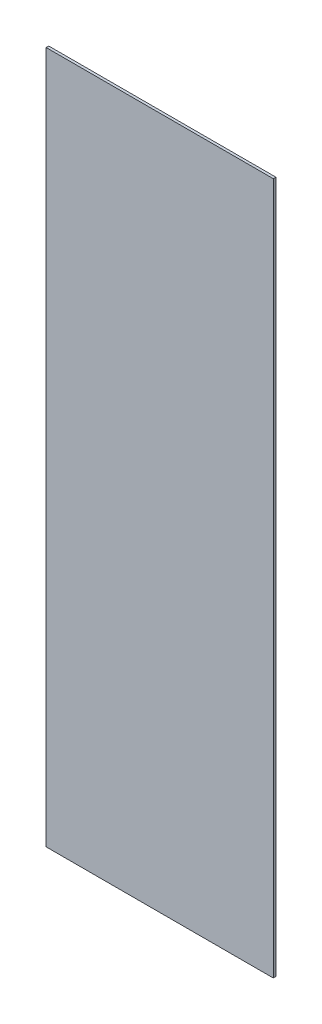
SolidWorks part; units mm, degrees
material "1060 Alloy"
ref_plane "Front Plane" through (0, 0, 0) normal (0, 0, 1) x (1, 0, 0)
ref_plane "Top Plane" through (0, 0, 0) normal (0, 1, 0) x (1, 0, 0)
ref_plane "Right Plane" through (0, 0, 0) normal (1, 0, 0) x (0, 0, -1)
sketch "Sketch1" plane through (0, 0, 0) normal (0, 0, 1) x (1, 0, 0)
  line L1 (-100, 304.8) -> (100, 304.8)
  line L2 (-100, 304.8) -> (-100, -304.8)
  line L3 (-100, -304.8) -> (100, -304.8)
  line L4 (100, 304.8) -> (100, -304.8)
  line L5 (-100, 304.8) -> (100, -304.8) construction
  line L6 (-100, -304.8) -> (100, 304.8) construction
  point P0 (0, 0)
  dimension "D1" = 609.6
  dimension "D2" = 200
extrude "Boss-Extrude1" add sketch "Sketch1" along normal blind 2.305
